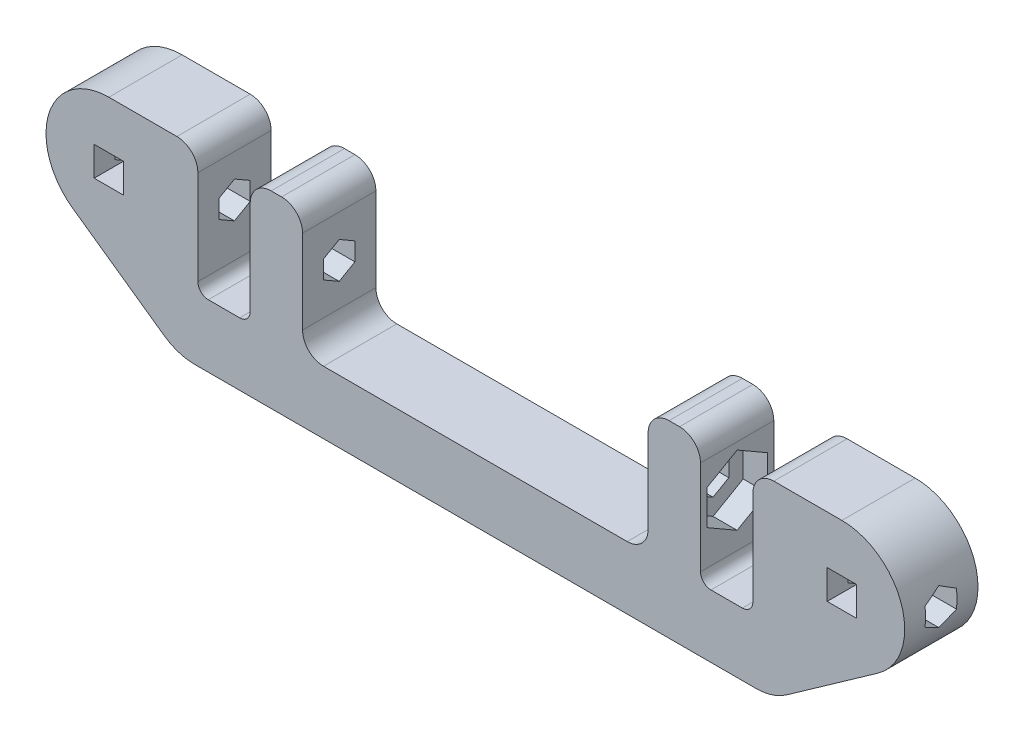
SolidWorks part; units mm, degrees
ref_plane "Front Plane" through (0, 0, 0) normal (0, 0, 1) x (1, 0, 0)
ref_plane "Top Plane" through (0, 0, 0) normal (0, 1, 0) x (1, 0, 0)
ref_plane "Right Plane" through (0, 0, 0) normal (1, 0, 0) x (0, 0, -1)
sketch "Sketch1" plane through (0, 0, 0) normal (0, 0, 1) x (1, 0, 0)
  line L0 (0, 0) -> (0, -6) construction
  line L1 (16.5, 0) -> (-16.5, 0)
  line L2 (-16.5, 0) -> (-16.5, 12)
  line L3 (-16.5, 12) -> (-21.5, 12)
  line L4 (-21.5, 12) -> (-21.5, 0)
  line L5 (-21.5, 0) -> (-26.5, 0)
  line L6 (-26.5, 0) -> (-26.5, 12)
  line L7 (-26.5, 12) -> (-35, 12)
  line L8 (-38.4601, 1.0982) -> (-28.4043, -6)
  line L9 (-28.4043, -6) -> (28.4043, -6)
  line L10 (38.4601, 1.0982) -> (28.4043, -6)
  line L11 (26.5, 12) -> (35, 12)
  line L12 (26.5, 0) -> (26.5, 12)
  line L13 (21.5, 0) -> (26.5, 0)
  line L14 (21.5, 12) -> (21.5, 0)
  line L15 (16.5, 12) -> (21.5, 12)
  line L16 (16.5, 0) -> (16.5, 12)
  line L17 (36.4, 7.4) -> (36.4, 4.6)
  line L18 (-33.6, 4.6) -> (-33.6, 7.4)
  line L19 (-33.6, 7.4) -> (-36.4, 7.4)
  line L20 (-36.4, 7.4) -> (-36.4, 4.6)
  line L21 (33.6, 7.4) -> (36.4, 7.4)
  line L22 (33.6, 4.6) -> (33.6, 7.4)
  line L23 (-36.4, 4.6) -> (-33.6, 4.6)
  line L24 (36.4, 4.6) -> (33.6, 4.6)
  line L25 (-26.5, 0) -> (-28.4043, -6) construction
  arc A0 (-35, 12) -> (-38.4601, 1.0982) centre (-35, 6) ccw
  arc A1 (35, 12) -> (38.4601, 1.0982) centre (35, 6) cw
  circle A2 centre (-35, 6) radius 1.4 construction
  point P17 (0, -6)
  dimension "D1" = 5
  dimension "D9" = 2.8
  dimension "D2" = 5
  dimension "D3" = 21.5
  dimension "D4" = 12
  dimension "D5" = 70
  dimension "D6" = 6
  dimension "D8" = 6
extrude "Boss-Extrude1" add sketch "Sketch1" along normal mid plane 7
sketch "Sketch2" plane through (0, 0, 0) normal (-1, 0, 0) x (0, 0, 1)
  line L0 (0, 7.7321) -> (-1.5, 6.866)
  line L1 (0, 4.2679) -> (1.5, 5.134)
  line L2 (1.5, 5.134) -> (1.5, 6.866)
  line L3 (1.5, 6.866) -> (0, 7.7321)
  line L4 (-1.5, 6.866) -> (-1.5, 5.134)
  line L5 (-1.5, 5.134) -> (0, 4.2679)
  circle A0 centre (0, 6) radius 1.5 construction
  dimension "D1" = 3
  dimension "D2" = 6
extrude "Cut-Extrude1" cut sketch "Sketch2" against normal through all and the other way through all
ref_axis "Axis1" through (-45.5651, 6, 0) along (1, 0, 0)
sketch "Sketch3" plane through (-21.5, 0, 0) normal (-1, 0, 0) x (0, 0, 1)
  line L0 (2.875, 7.6599) -> (0, 9.3198)
  line L1 (-2.875, 7.6599) -> (-2.875, 4.3401)
  line L2 (-2.875, 4.3401) -> (0, 2.6802)
  line L3 (0, 2.6802) -> (2.875, 4.3401)
  line L4 (2.875, 4.3401) -> (2.875, 7.6599)
  line L5 (0, 9.3198) -> (-2.875, 7.6599)
  circle A0 centre (0, 6) radius 2.875 construction
  dimension "D1" = 5.75
extrude "Cut-Extrude2" cut sketch "Sketch3" against normal blind 2.3
mirror "Mirror1" about plane through (0, 0, 0) normal (1, 0, 0) of "Cut-Extrude2"
fillet "Fillet1" radius 2 8 edges at (-16.5, 0, 0) (16.5, 0, 0) (-26.5, 12, 0) (26.5, 12, 0) (21.5, 12, 0) (16.5, 12, 0) (-21.5, 12, 0) (-16.5, 12, 0)
fillet "Fillet2" radius 5 2 edges at (28.4043, -6, 0) (-28.4043, -6, 0)
ref_axis "Axis2" through (-35, 6, -4.0653) along (0, 0, 1)
ref_axis "Axis3" through (35, 6, -3.9636) along (0, 0, 1)
fillet "Fillet3" radius 1 4 edges at (26.5, 0, 0) (21.5, 0, 0) (-26.5, 0, 0) (-21.5, 0, 0)
